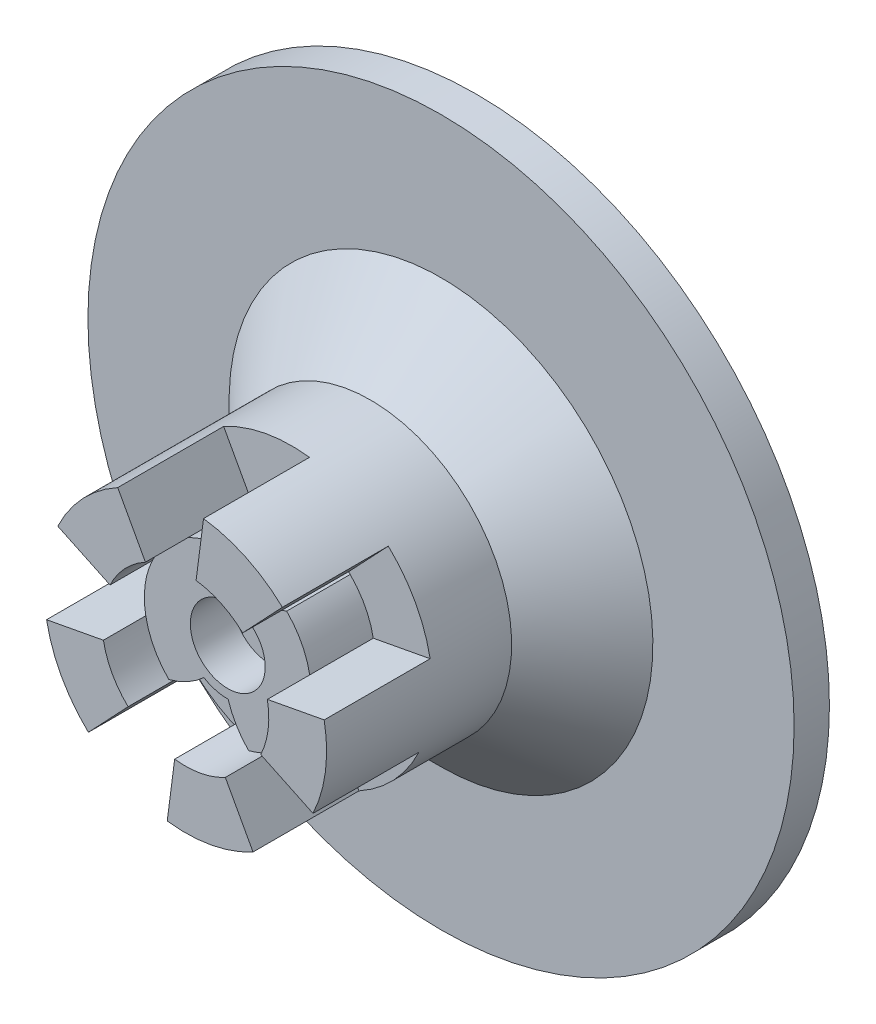
SolidWorks part; units mm, degrees
note: The reader was unsure of these and kept them because the rebuilt part matched: shared geometry of "Sketch11<5>", "Sketch11<6>".
ref_plane "Front Plane" through (0, 0, 0) normal (0, 0, 1) x (1, 0, 0)
ref_plane "Top Plane" through (0, 0, 0) normal (0, 1, 0) x (1, 0, 0)
ref_plane "Right Plane" through (0, 0, 0) normal (1, 0, 0) x (0, 0, -1)
sketch "Sketch2" plane through (0, 0, 0) normal (1, 0, 0) x (0, 0, -1)
  line L0 (-13.081, 0) -> (-13.081, 9.525)
  line L1 (-13.081, -31.75) -> (13.081, -31.75) construction
  line L2 (-13.081, -31.75) -> (-13.081, 9.525) construction
  line L3 (-9.906, 31.75) -> (13.081, 31.75) construction
  line L4 (13.081, -31.75) -> (13.081, 31.75) construction
  line L5 (-13.081, -31.75) -> (13.081, 31.75) construction
  line L6 (-13.081, 31.75) -> (-9.906, 24.0437) construction
  line L7 (-13.081, 31.75) -> (-9.906, 31.75) construction
  line L8 (-9.906, 31.75) -> (-9.906, 24.0437) construction
  line L9 (-9.906, 12.7) -> (9.906, 12.7)
  line L10 (9.906, 12.7) -> (9.906, 31.75)
  line L11 (9.906, 31.75) -> (13.081, 31.75)
  line L12 (13.081, 31.75) -> (13.081, 0)
  line L13 (13.081, 0) -> (-13.081, 0)
  line L14 (-13.081, -31.75) -> (-13.081, 0) construction
  line L15 (-9.906, 12.7) -> (-13.081, 12.7)
  line L16 (-9.906, 24.0437) -> (-5.2324, 12.7) construction
  line L17 (-5.2324, 12.7) -> (13.081, -31.75) construction
  line L18 (-9.906, 24.0437) -> (-9.906, 12.7) construction
  line L19 (-13.081, 12.7) -> (-13.081, 31.75) construction
  line L20 (-13.081, 12.7) -> (-13.081, 31.75) construction
  line L21 (-13.081, 31.75) -> (-9.906, 31.75) construction
  line L22 (-9.906, 12.7) -> (-9.906, 9.525) construction
  line L23 (-9.906, 9.525) -> (-13.081, 9.525) construction
  line L24 (-13.081, 9.525) -> (-13.081, 12.7)
  line L25 (-13.081, 9.525) -> (-13.081, 12.7) construction
  point P0 (0, 0)
  dimension "D1" = 63.5
  dimension "D2" = 26.162
  dimension "D3" = 3.175
  dimension "D4" = 12.7
  dimension "D5" = 3.175
  dimension "D6" = 9.525
revolve "Revolve1" add sketch "Sketch2" angle 360 about L13
sketch "Sketch11" plane through (0, 0, 13.081) normal (0, 0, 1) x (1, 0, 0)
  circle A0 centre (0, 0) radius 3.3672 construction
  arc A1 (5.2954, 5.3111) -> (2.1471, 3.5864) centre (7.2397, -1.9739) ccw construction
  arc A2 (2.1471, 3.5864) -> (-0.0336, 4.1799) centre (0, 0) ccw construction
  arc A3 (0.0336, -4.1799) -> (1.8738, -7.2621) centre (7.2416, -1.967) ccw construction
  arc A4 (-2.1471, -3.5864) -> (0.0336, -4.1799) centre (0, 0) ccw construction
  arc A5 (-0.0336, 4.1799) -> (-1.8738, 7.2621) centre (-7.2416, 1.967) ccw construction
  arc A6 (-5.2954, -5.3111) -> (-2.1471, -3.5864) centre (-7.2397, 1.9739) ccw construction
  circle A7 centre (0, 0) radius 7.5 construction
  circle A8 centre (0, 0) radius 3.3672
  arc A9 (5.2954, 5.3111) -> (2.1471, 3.5864) centre (7.2397, -1.9739) ccw
  arc A10 (2.1471, 3.5864) -> (-0.0336, 4.1799) centre (0, 0) ccw
  arc A11 (0.0336, -4.1799) -> (1.8738, -7.2621) centre (7.2416, -1.967) ccw
  arc A12 (-2.1471, -3.5864) -> (0.0336, -4.1799) centre (0, 0) ccw
  arc A13 (-0.0336, 4.1799) -> (-1.8738, 7.2621) centre (-7.2416, 1.967) ccw
  arc A14 (-5.2954, -5.3111) -> (-2.1471, -3.5864) centre (-7.2397, 1.9739) ccw
  circle A15 centre (0, 0) radius 7.5
extrude "Cut-Extrude5" cut sketch "Sketch11" against normal blind 3.81 contours A14 A15 A11 A12 | A13 A15 A14 A12 A11 A9 A10 A8 | A8 | A9 A15 A13 A10
extrude "Cut-Extrude7" cut sketch "Sketch11<5>" against normal blind 7.62 contours A8
sketch "Sketch11<5>" plane through (0, 0, 13.081) normal (0, 0, 1) x (1, 0, 0) same geometry as "Sketch11"
extrude "Cut-Extrude8" cut sketch "Sketch11<6>" against normal blind 10.16 contours A14 A15 A11 A12 | A9 A15 A13 A10
sketch "Sketch11<6>" plane through (0, 0, 13.081) normal (0, 0, 1) x (1, 0, 0) same geometry as "Sketch11"
sketch "Sketch13" plane through (0, 0, -13.081) normal (0, 0, -1) x (-1, 0, 0)
  circle A0 centre (0, 0) radius 6.35
extrude "Cut-Extrude10" cut sketch "Sketch13" against normal blind 12.192
chamfer "Chamfer1" distance 5.842 angle 45 1 edges at (-6.35, 0, -0.889)
chamfer "Chamfer2" distance 6.35 angle 45 1 edges at (0, 12.7, -9.906)
sketch "Sketch14" plane through (0, 0, 13.081) normal (0, 0, 1) x (1, 0, 0)
  line L0 (12.4826, 2.3398) -> (7.3716, 1.3818) construction
  line L1 (11.4739, -5.4442) -> (6.7759, -3.2151) construction
  line L2 (-11.4739, 5.4442) -> (-6.7759, 3.2151)
  line L3 (-3.5921, 6.5838) -> (-6.0826, 11.1486)
  line L4 (-11.4739, 5.4442) -> (-6.7759, 3.2151)
  line L5 (-3.5921, 6.5838) -> (-6.0826, 11.1486)
  line L6 (-8.7234, -9.23) -> (-5.1516, -5.4508)
  line L7 (-7.3716, -1.3818) -> (-12.4826, -2.3398)
  line L8 (-8.7234, -9.23) -> (-5.1516, -5.4508)
  line L9 (-7.3716, -1.3818) -> (-12.4826, -2.3398)
  line L10 (-0.9638, -7.4378) -> (-1.6321, -12.5947)
  line L11 (6.0826, -11.1486) -> (3.5921, -6.5838)
  line L12 (-0.9638, -7.4378) -> (-1.6321, -12.5947)
  line L13 (6.0826, -11.1486) -> (3.5921, -6.5838)
  line L14 (5.1516, 5.4508) -> (8.7234, 9.23)
  line L15 (1.6321, 12.5947) -> (0.9638, 7.4378)
  line L16 (5.1516, 5.4508) -> (8.7234, 9.23)
  line L17 (1.6321, 12.5947) -> (0.9638, 7.4378)
  line L18 (12.4826, 2.3398) -> (7.3716, 1.3818)
  line L19 (11.4739, -5.4442) -> (6.7759, -3.2151)
  arc A0 (-0.9638, -7.4378) -> (3.5921, -6.5838) centre (0, 0) ccw construction
  circle A1 centre (0, 0) radius 7.5
  circle A2 centre (0, 0) radius 7.5
  arc A3 (11.4739, -5.4442) -> (12.4826, 2.3398) centre (0, 0) ccw construction
  arc A4 (-3.5921, 6.5838) -> (-6.7759, 3.2151) centre (0, 0) ccw
  arc A5 (-6.0826, 11.1486) -> (-11.4739, 5.4442) centre (0, 0) ccw
  arc A6 (-3.5921, 6.5838) -> (-6.7759, 3.2151) centre (0, 0) ccw
  arc A7 (-6.0826, 11.1486) -> (-11.4739, 5.4442) centre (0, 0) ccw
  arc A8 (-7.3716, -1.3818) -> (-5.1516, -5.4508) centre (0, 0) ccw
  arc A9 (-12.4826, -2.3398) -> (-8.7234, -9.23) centre (0, 0) ccw
  arc A10 (-7.3716, -1.3818) -> (-5.1516, -5.4508) centre (0, 0) ccw
  arc A11 (-12.4826, -2.3398) -> (-8.7234, -9.23) centre (0, 0) ccw
  arc A12 (-0.9638, -7.4378) -> (3.5921, -6.5838) centre (0, 0) ccw
  arc A13 (-1.6321, -12.5947) -> (6.0826, -11.1486) centre (0, 0) ccw
  arc A14 (-0.9638, -7.4378) -> (3.5921, -6.5838) centre (0, 0) ccw
  arc A15 (-1.6321, -12.5947) -> (6.0826, -11.1486) centre (0, 0) ccw
  arc A16 (5.1516, 5.4508) -> (0.9638, 7.4378) centre (0, 0) ccw
  arc A17 (8.7234, 9.23) -> (1.6321, 12.5947) centre (0, 0) ccw
  arc A18 (5.1516, 5.4508) -> (0.9638, 7.4378) centre (0, 0) ccw
  arc A19 (8.7234, 9.23) -> (1.6321, 12.5947) centre (0, 0) ccw
  arc A20 (-3.5921, 6.5838) -> (-6.7759, 3.2151) centre (0, 0) ccw construction
  arc A21 (-7.3716, -1.3818) -> (-5.1516, -5.4508) centre (0, 0) ccw construction
  arc A22 (5.1516, 5.4508) -> (0.9638, 7.4378) centre (0, 0) ccw construction
  arc A23 (-0.9638, -7.4378) -> (3.5921, -6.5838) centre (0, 0) ccw
  arc A24 (11.4739, -5.4442) -> (12.4826, 2.3398) centre (0, 0) ccw
  arc A25 (-3.5921, 6.5838) -> (-6.7759, 3.2151) centre (0, 0) ccw
  arc A26 (-7.3716, -1.3818) -> (-5.1516, -5.4508) centre (0, 0) ccw
  arc A27 (5.1516, 5.4508) -> (0.9638, 7.4378) centre (0, 0) ccw
  dimension "D1" = 0
  dimension "D2" = 0
  dimension "D3" = 0
  dimension "D4" = 0
  dimension "D5" = 0
extrude "Cut-Extrude11" cut sketch "Sketch14" against normal blind 9.525
